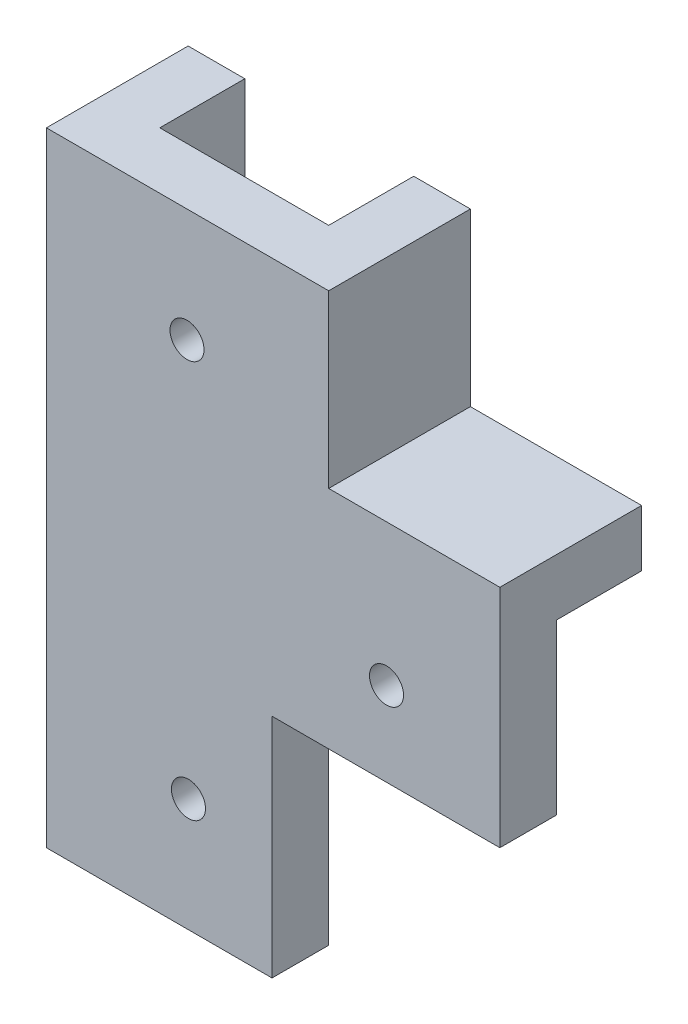
SolidWorks part; units mm, degrees
ref_plane "前视基准面" through (0, 0, 0) normal (0, 0, 1) x (1, 0, 0)
ref_plane "上视基准面" through (0, 0, 0) normal (0, 1, 0) x (1, 0, 0)
ref_plane "右视基准面" through (0, 0, 0) normal (1, 0, 0) x (0, 0, -1)
sketch "Sketch1" plane through (0, 0, 0) normal (0, 0, 1) x (1, 0, 0)
  line L0 (7.3701, -25.8068) -> (27.4701, -25.8068)
  line L3 (-7.5299, 9.1932) -> (7.3701, 9.1932)
  line L4 (-7.5299, 9.1932) -> (-7.5299, -25.8068)
  line L6 (7.3701, 9.1932) -> (7.3701, -10.9068)
  line L7 (27.4701, -25.8068) -> (27.4701, -10.9068)
  line L8 (27.4701, -10.9068) -> (7.3701, -10.9068)
  line L12 (-7.5299, -25.8068) -> (7.3701, -25.8068)
  dimension "D1" = 14.9
  dimension "D2" = 35
  dimension "D3" = 35
  dimension "D4" = 14.9
extrude "Boss-Extrude1" add sketch "Sketch1" along normal blind 5
sketch "Sketch2" plane through (0, 0, 0) normal (0, 0, -1) x (-1, 0, 0)
  line L0 (-7.3701, 9.1932) -> (-12.3701, 9.1932)
  line L1 (-12.3701, 9.1932) -> (-12.3701, -5.9068)
  line L2 (-12.3701, -5.9068) -> (-27.4701, -5.9068)
  line L3 (-27.4701, -10.9068) -> (-27.4701, -5.9068)
  line L4 (-27.4701, -10.9068) -> (-7.3701, -10.9068)
  line L5 (-7.3701, -10.9068) -> (-7.3701, 9.1932)
  dimension "D1" = 5
  dimension "D2" = 5
extrude "Boss-Extrude2" add sketch "Sketch2" along normal blind 7.5 separate body
sketch "Sketch3" plane through (0, 0, 0) normal (0, 0, -1) x (-1, 0, 0)
  line L0 (7.5299, 9.1932) -> (12.5299, 9.1932)
  line L2 (12.5299, -45.8068) -> (12.5299, 9.1932)
  line L3 (7.5299, -25.8068) -> (7.5299, 9.1932)
  line L5 (7.5299, -25.8068) -> (7.5299, -45.8068)
  line L6 (7.5299, -45.8068) -> (12.5299, -45.8068)
  dimension "D1" = 5
  dimension "D2" = 55
extrude "Boss-Extrude3" add sketch "Sketch3" along normal blind 7.5 separate body
sketch "Sketch4" plane through (0, 0, 0) normal (0, 0, -1) x (-1, 0, 0)
  line L0 (-27.4701, -10.9068) -> (-7.3701, -10.9068) construction
  line L1 (-27.4701, -25.8068) -> (-27.4701, -10.9068) construction
  line L2 (-7.3701, -10.9068) -> (-7.3701, 9.1932) construction
  line L3 (-7.3701, 9.1932) -> (7.5299, 9.1932) construction
  circle A0 centre (0.1299, -0.8068) radius 1.5
  circle A1 centre (-17.4701, -18.4068) radius 1.5
  dimension "D1" = 3
  dimension "D2" = 3
  dimension "D3" = 7.5
  dimension "D4" = 10
  dimension "D5" = 7.5
  dimension "D6" = 10
extrude "Cut-Extrude1" cut sketch "Sketch4" against normal through all
sketch "Sketch6" plane through (0, 0, 5) normal (0, 0, 1) x (1, 0, 0)
  line L0 (-7.5299, -25.8068) -> (-7.5299, -45.8068)
  line L1 (-7.5299, -25.8068) -> (27.4701, -25.8068) construction
  line L2 (-7.5299, -45.8068) -> (7.3701, -45.8068)
  line L3 (7.3701, -45.8068) -> (7.3701, -25.8068)
  line L4 (7.3701, -25.8068) -> (-7.5299, -25.8068)
  dimension "D1" = 14.9
  dimension "D2" = 20
extrude "Boss-Extrude4" add sketch "Sketch6" against normal blind 5
sketch "Sketch8" plane through (0, 0, 5) normal (0, 0, 1) x (1, 0, 0)
  line L0 (-7.5299, -45.8068) -> (7.3701, -45.8068) construction
  circle A0 centre (0, -35.8068) radius 1.5
  dimension "D1" = 3
  dimension "D2" = 10
extrude "Cut-Extrude3" cut sketch "Sketch8" against normal through all contours A0
sketch "Sketch9" plane through (0, 0, 5) normal (0, 0, 1) x (1, 0, 0)
  line L1 (-12.5299, 9.1932) -> (-7.5299, 9.1932)
  line L2 (-12.5299, 9.1932) -> (-12.5299, -45.8068)
  line L3 (-12.5299, -45.8068) -> (-7.5299, -45.8068)
  line L4 (-7.5299, 9.1932) -> (-7.5299, -45.8068)
extrude "Boss-Extrude5" add sketch "Sketch9" against normal blind 5
sketch "Sketch10" plane through (0, 0, 0) normal (0, 0, 1) x (1, 0, 0)
  line L0 (7.3701, 9.1932) -> (12.3701, 9.1932)
  line L1 (7.3701, 9.1932) -> (12.3701, 9.1932) construction
  line L2 (12.3701, 9.1932) -> (12.3701, -5.9068)
  line L3 (12.3701, -5.9068) -> (27.4701, -5.9068)
  line L4 (12.3701, -5.9068) -> (27.4701, -5.9068) construction
  line L5 (27.4701, -5.9068) -> (27.4701, -10.9068) construction
  line L6 (27.4701, -5.9068) -> (27.4701, -10.9068)
  line L7 (27.4701, -10.9068) -> (7.3701, -10.9068)
  line L8 (7.3701, -10.9068) -> (7.3701, 9.1932)
extrude "Boss-Extrude6" add sketch "Sketch10" along normal blind 5
